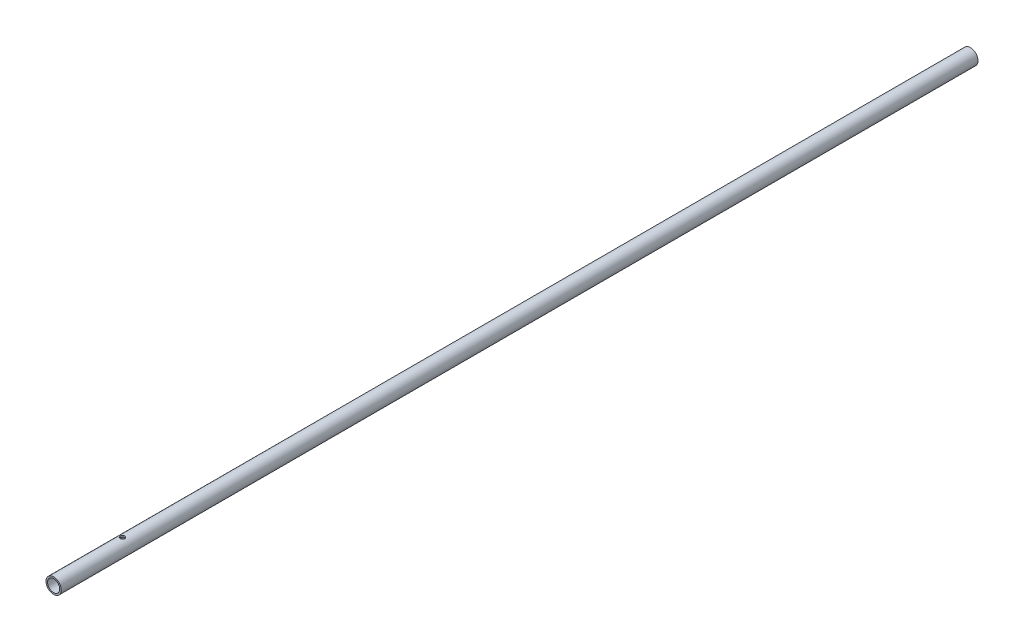
SolidWorks part; units mm, degrees
material "Thornel Mat VMA"
ref_plane "前视基准面" through (0, 0, 0) normal (0, 0, 1) x (1, 0, 0)
ref_plane "上视基准面" through (0, 0, 0) normal (0, 1, 0) x (1, 0, 0)
ref_plane "右视基准面" through (0, 0, 0) normal (1, 0, 0) x (0, 0, -1)
other "Configuration Table"
sketch "草图1" plane through (0, 0, 0) normal (0, 0, 1) x (1, 0, 0)
  circle A0 centre (0, 0) radius 5
  circle A1 centre (0, 0) radius 4
  dimension "D1" = 10
  dimension "D2" = 1
extrude "凸台-拉伸1" add sketch "草图1" along normal blind 600
sketch "草图2" plane through (0, 0, 0) normal (0, 1, 0) x (1, 0, 0)
  circle A0 centre (0, -31.3344) radius 1.5
  dimension "D1" = 3
  dimension "D2" = 31.3344
extrude "切除-拉伸1" cut sketch "草图2" against normal through all
sketch "草图3" plane through (0, 0, 0) normal (0, 1, 0) x (1, 0, 0)
  circle A0 centre (0, -555) radius 1.5
  point P3 (0, 0)
  point P4 (3.3276, -629.5872)
  point P5 (0, -555)
  dimension "D1" = 3
extrude "切除-拉伸2" cut sketch "草图3" along normal through all
